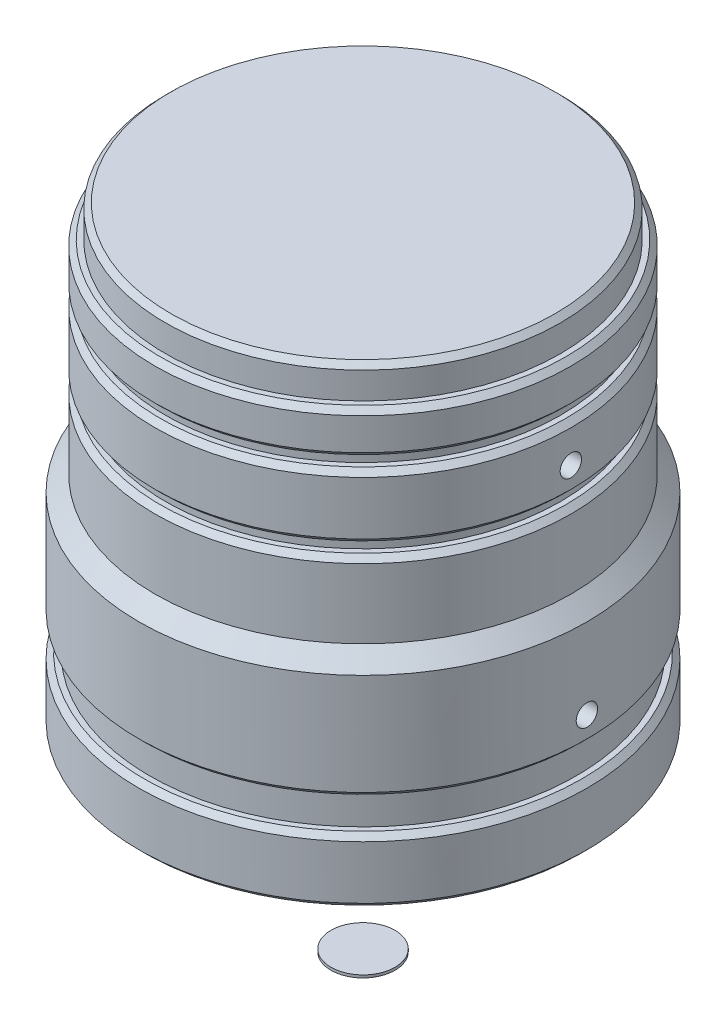
SolidWorks part; units mm, degrees
ref_plane "Front Plane" through (0, 0, 0) normal (0, 0, 1) x (1, 0, 0)
ref_plane "Top Plane" through (0, 0, 0) normal (0, 1, 0) x (1, 0, 0)
ref_plane "Right Plane" through (0, 0, 0) normal (1, 0, 0) x (0, 0, -1)
sketch "Sketch1" plane through (0, 0, 0) normal (0, 0, 1) x (1, 0, 0)
  line L0 (0, 0) -> (18.5, 0)
  line L1 (18.5, 0) -> (18.5, -3)
  line L2 (18.5, -3) -> (19.5, -3)
  line L3 (19.5, -3) -> (19.5, -7)
  line L4 (19.5, -7) -> (18.5, -7)
  line L5 (18.5, -7) -> (18.5, -8)
  line L6 (18.5, -8) -> (19.5, -8)
  line L7 (19.5, -8) -> (19.5, -14)
  line L8 (19.5, -14) -> (18.5, -14)
  line L9 (18.5, -14) -> (18.5, -15)
  line L10 (18.5, -15) -> (19.5, -15)
  line L11 (19.5, -15) -> (19.5, -22)
  line L12 (19.5, -22) -> (21, -22)
  line L13 (21, -22) -> (21, -33.5)
  line L14 (21, -33.5) -> (20, -33.5)
  line L15 (20, -33.5) -> (20, -36.5)
  line L16 (20, -36.5) -> (21, -36.5)
  line L17 (21, -36.5) -> (21, -42.5)
  line L18 (21, -42.5) -> (18, -42.5)
  line L19 (18, -42.5) -> (18, -43)
  line L20 (18, -43) -> (12.18, -43)
  line L21 (12.18, -43) -> (12.18, -43.75)
  line L22 (12.18, -43.75) -> (12.7, -43.75)
  line L23 (12.7, -43.75) -> (12.7, -47)
  line L24 (12.7, -47) -> (0, -47)
  line L25 (0, 0) -> (0, -47)
revolve "Lens Body" add sketch "Sketch1" angle 360 about L25
chamfer ".5mm Body Chamfers" distance 0.5 10 edges at (-18.5, 0, 0) (-19.5, -15, 0) (-19.5, -14, 0) (-19.5, -8, 0) (-19.5, -7, 0) (-19.5, -3, 0) (-21, -33.5, 0) (-21, -42.5, 0) (-21, -36.5, 0) (-18, -43, 0)
chamfer "1.5mm Body Chamfers" distance 1.5 angle 45 1 edges at (-21, -22, 0)
chamfer ".48mm x .28mm Body Chamfer 1" distance 0.28 distance2 0.48 1 edges at (-12.7, -43.75, 0) first distance on face at (-12.7, -43.75, 0)
chamfer ".48mm x .28mm Body Chamfer 2" distance 0.48 distance2 0.28 1 edges at (-12.7, -47, 0) first distance on face at (-12.7, -47, 0)
sketch "Sketch2" plane through (0, -47, 0) normal (0, -1, 0) x (1, 0, 0)
  circle A0 centre (0, 0) radius 9
extrude "Sensor Hole" cut sketch "Sketch2" against normal blind 10
ref_plane "Focal Plane" through (0, -60.78, 0) normal (0, 1, 0) x (1, 0, 0)
sketch "Sketch9" plane through (0, -60.78, 0) normal (0, 1, 0) x (1, 0, 0)
  circle A0 centre (0, 0) radius 3
extrude "Focal Point" add sketch "Sketch9" along normal blind 0.25 separate body
ref_plane "Plane1" through (21, 0, 0) normal (1, 0, 0) x (0, 0, -1)
ref_plane "Plane2" through (19.5, 0, 0) normal (1, 0, 0) x (0, 0, -1)
sketch "Sketch10" plane through (21, 0, 0) normal (1, 0, 0) x (0, 0, -1)
  line L0 (-21, -33) -> (21, -33) construction
  circle A0 centre (0, -31.05) radius 1
  dimension "D2" = 2
  dimension "D1" = 1.95
extrude "Cut-Extrude1" cut sketch "Sketch10" against normal blind 2
sketch "Sketch11" plane through (19.5, 0, 0) normal (1, 0, 0) x (0, 0, -1)
  line L0 (-19.5, -13.5) -> (19.5, -13.5) construction
  circle A0 centre (0, -11.55) radius 1
  dimension "D2" = 2
  dimension "D1" = 1.95
extrude "Cut-Extrude2" cut sketch "Sketch11" against normal blind 2
